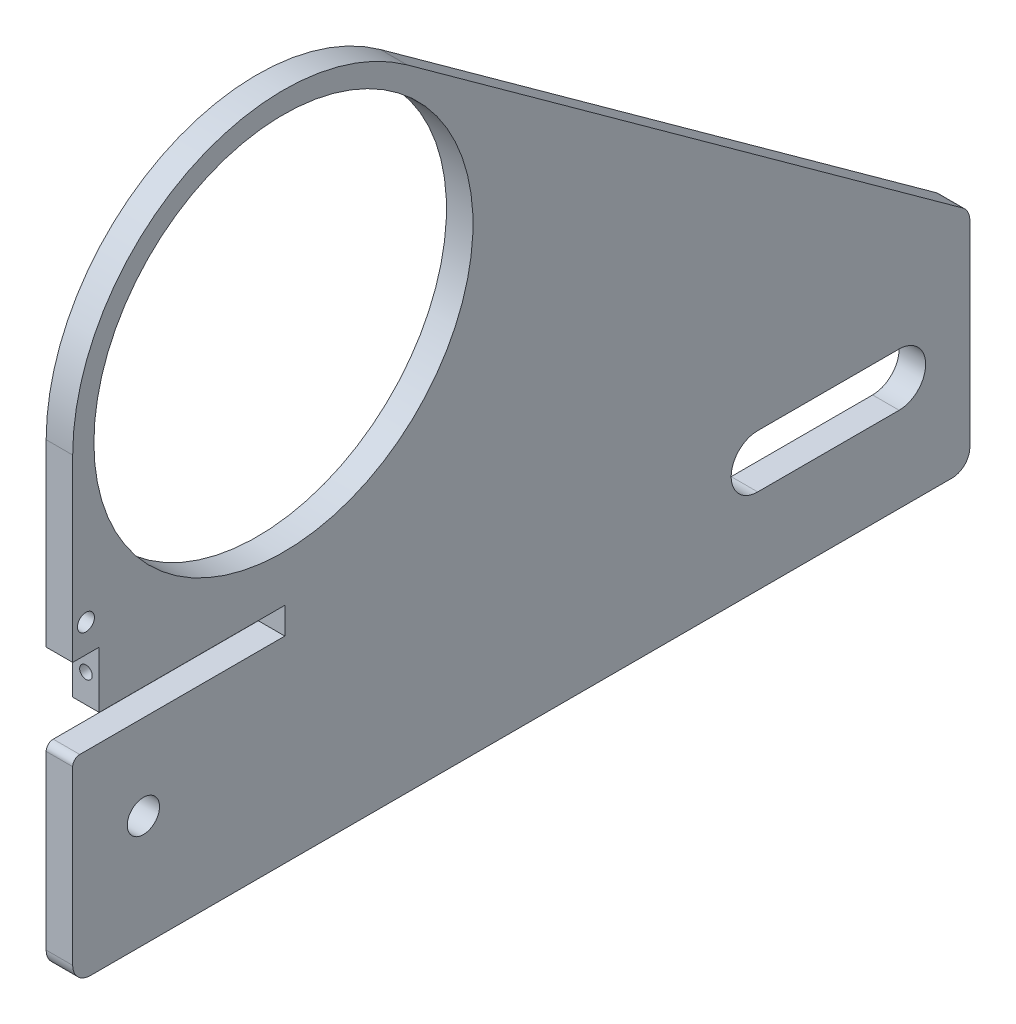
SolidWorks part; units mm, degrees
ref_plane "Front Plane" through (0, 0, 0) normal (0, 0, 1) x (1, 0, 0)
ref_plane "Top Plane" through (0, 0, 0) normal (0, 1, 0) x (1, 0, 0)
ref_plane "Right Plane" through (0, 0, 0) normal (1, 0, 0) x (0, 0, -1)
sketch "Sketch1" plane through (0, 0, 0) normal (1, 0, 0) x (0, 0, -1)
  line L0 (-77.3828, 0) -> (77.3828, 0)
  line L1 (80.5578, 3.175) -> (80.5578, 38.5097)
  line L2 (-80.5578, 82.55) -> (-80.5578, 50.292)
  line L3 (79.2431, 41.0826) -> (-20.5306, 113.2224)
  line L4 (-75.7953, 50.292) -> (-75.7953, 40.132)
  line L5 (67.8578, 20.066) -> (42.4578, 20.066) construction
  line L6 (67.8578, 15.3035) -> (42.4578, 15.3035)
  line L7 (-75.7953, 40.132) -> (-42.4578, 40.132)
  line L8 (-42.4578, 40.132) -> (-42.4578, 35.3441)
  line L9 (-42.4578, 35.3441) -> (-79.2878, 35.3441)
  line L10 (-80.5578, 34.0741) -> (-80.5578, 3.175)
  line L11 (-80.5578, 50.292) -> (-75.7953, 50.292)
  line L12 (67.8578, 24.8285) -> (42.4578, 24.8285)
  arc A0 (67.8578, 15.3035) -> (67.8578, 24.8285) centre (67.8578, 20.066) ccw
  circle A1 centre (-42.7078, 82.55) radius 31.5 construction
  circle A2 centre (67.8578, 20.066) radius 76.2 construction
  circle A3 centre (-78.1765, 55.372) radius 1.524
  arc A4 (42.4578, 24.8285) -> (42.4578, 15.3035) centre (42.4578, 20.066) ccw
  arc A5 (-20.5306, 113.2224) -> (-80.5578, 82.55) centre (-42.7078, 82.55) ccw
  arc A6 (-77.3828, 0) -> (-80.5578, 3.175) centre (-77.3828, 3.175) cw
  arc A7 (77.3828, 0) -> (80.5578, 3.175) centre (77.3828, 3.175) ccw
  arc A8 (80.5578, 38.5097) -> (79.2431, 41.0826) centre (77.3828, 38.5097) ccw
  arc A9 (-79.2878, 35.3441) -> (-80.5578, 34.0741) centre (-79.2878, 34.0741) ccw
  circle A11 centre (-67.8578, 20.066) radius 2.8956
  circle A16 centre (-42.7078, 82.55) radius 34.04
  point P13 (55.1578, 20.066)
  point P14 (0, 0)
  point P28 (80.5578, 40.132)
  dimension "D4" = 9.525
  dimension "D7" = 4.7625
  dimension "D8" = 63
  dimension "D9" = 6.35
  dimension "D12" = 3.175
  dimension "D13" = 1.27
  dimension "D14" = 2.54
  dimension "D15" = 152.4
  dimension "D18" = 5.7912
  dimension "D19" = 5.08
  dimension "D20" = 12.7
  dimension "D17" = 3.048
  dimension "D1" = 4.7879
  dimension "D2" = 40.132
  dimension "D3" = 20.066
  dimension "D5" = 12.7
  dimension "D6" = 38.1
  dimension "D10" = 127
  dimension "D11" = 82.55
  dimension "D21" = 25.4
  dimension "D22" = 10.16
  dimension "D16" = 2.3813
extrude "Boss-Extrude1" add sketch "Sketch1" along normal blind 4.7625
sketch "Sketch2" plane through (0, 0, 75.7953) normal (0, 0, 1) x (1, 0, 0)
  line L0 (0, 50.292) -> (0, 40.132) construction
  line L1 (4.7625, 40.132) -> (0, 40.132) construction
  circle A0 centre (2.3813, 45.212) radius 1.1303
  point P4 (0, 45.212)
  point P7 (2.3813, 40.132)
  dimension "D1" = 2.2606
extrude "Cut-Extrude1" cut sketch "Sketch2" against normal blind 6.35
